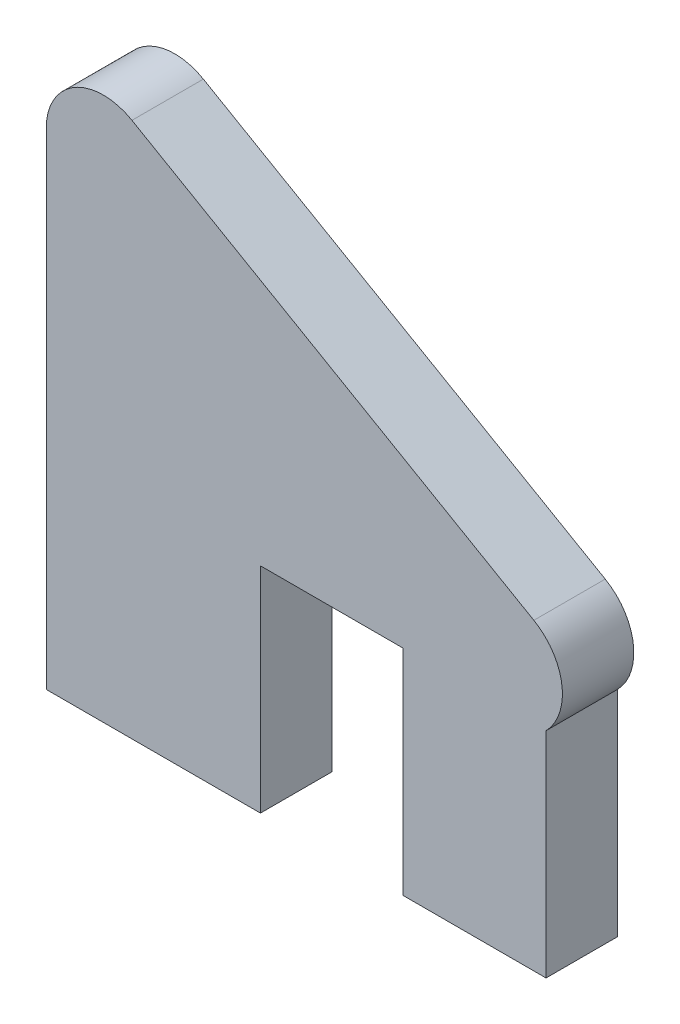
SolidWorks part; units mm, degrees
ref_plane "Front Plane" through (0, 0, 0) normal (0, 0, 1) x (1, 0, 0)
ref_plane "Top Plane" through (0, 0, 0) normal (0, 1, 0) x (1, 0, 0)
ref_plane "Right Plane" through (0, 0, 0) normal (1, 0, 0) x (0, 0, -1)
sketch "Sketch1" plane through (0, 0, 0) normal (0, 0, 1) x (1, 0, 0)
  line L0 (0, 0) -> (28.575, 0)
  line L1 (0, 0) -> (9.525, 0)
  line L2 (0, 0) -> (0, -9.525)
  line L3 (0, -9.525) -> (9.525, -9.525)
  line L4 (9.525, 0) -> (9.525, -9.525)
  line L5 (15.875, 0) -> (22.225, 0)
  line L6 (15.875, 0) -> (15.875, -9.525)
  line L7 (15.875, -9.525) -> (22.225, -9.525)
  line L8 (22.225, 0) -> (22.225, -9.525)
  line L9 (28.575, 0) -> (0, 16.4978)
  line L10 (0, 16.4978) -> (0, 0)
  dimension "D1" = 9.525
  dimension "D2" = 9.525
  dimension "D3" = 6.35
  dimension "D4" = 6.35
  dimension "D5" = 28.575
  dimension "D6" = 30
extrude "Boss-Extrude1" add sketch "Sketch1" along normal blind 3.175 contours L4 L0 L2 L3 | L9 L10 L0 | L8 L0 L6 L7 region at (9.525, 5.4993, 0) region at (4.7625, -4.7625, 0) region at (19.05, -4.7625, 0)
fillet "Fillet1" radius 2.54 2 edges at (28.575, 0, 1.5875) (0, 16.4978, 1.5875)
